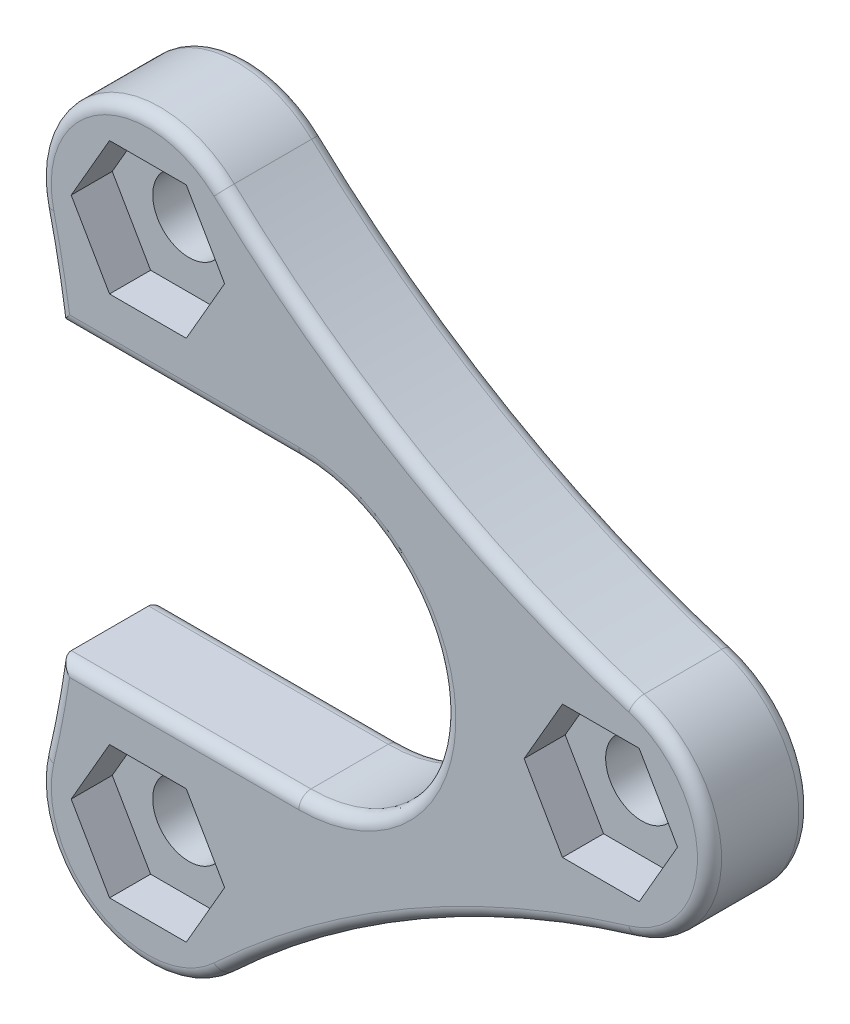
SolidWorks part; units mm, degrees
ref_plane "Front Plane" through (0, 0, 0) normal (0, 0, 1) x (1, 0, 0)
ref_plane "Top Plane" through (0, 0, 0) normal (0, 1, 0) x (1, 0, 0)
ref_plane "Right Plane" through (0, 0, 0) normal (1, 0, 0) x (0, 0, -1)
sketch "Sketch-Reference-Single" plane through (0, 0, 0) normal (0, 0, 1) x (1, 0, 0)
  circle A0 centre (-12.5, 0) radius 1.5
  circle A1 centre (-6.25, 10.8253) radius 1.5
  circle A2 centre (6.25, 10.8253) radius 1.5
  circle A3 centre (12.5, 0) radius 1.5
  circle A4 centre (6.25, -10.8253) radius 1.5
  circle A5 centre (-6.25, -10.8253) radius 1.5
  point P14 (0, 0)
sketch "Sketch-Reference-Dual" plane through (0, 0, 0) normal (0, 0, 1) x (1, 0, 0)
  line L0 (0, 0) -> (-12, 0) construction
  line L1 (0, 0) -> (0, -8.1544) construction
  circle A0 centre (-18, 10.3923) radius 1.5
  circle A1 centre (0, 0) radius 1.5
  circle A2 centre (-18, -10.3923) radius 1.5
  circle A3 centre (18, -10.3923) radius 1.5
  circle A4 centre (18, 10.3923) radius 1.5
  point P11 (-12, 0)
sketch "Sketch1" plane through (0, 0, 0) normal (0, 0, 1) x (1, 0, 0)
  line L0 (0, -8.1544) -> (0, 0) construction
  line L1 (-12, 0) -> (0, 0) construction
  line L2 (-12, 6) -> (-18.9786, 6)
  line L3 (-12, -6) -> (-18.9786, -6)
  line L4 (12, -6) -> (18.9786, -6)
  line L5 (12, 6) -> (18.9786, 6)
  line L6 (0, 0) -> (0, 10.3923) construction
  arc A0 (-12, -6) -> (-12, 6) centre (-12, 0) ccw
  arc A1 (-15.8824, -14.3629) -> (-18.9786, -6) centre (-18, -10.3923) cw
  arc A2 (15.8824, -14.3629) -> (18.9786, -6) centre (18, -10.3923) ccw
  circle A3 centre (-18, 10.3923) radius 4.5
  arc A4 (-15.8824, 14.3629) -> (-18.9786, 6) centre (-18, 10.3923) ccw
  arc A5 (12, -6) -> (12, 6) centre (12, 0) cw
  arc A6 (15.8824, 14.3629) -> (18.9786, 6) centre (18, 10.3923) cw
  arc A7 (-15.8824, 14.3629) -> (15.8824, 14.3629) centre (0, 44.1423) ccw
  arc A8 (-15.8824, -14.3629) -> (15.8824, -14.3629) centre (0, -44.1423) cw
  circle A9 centre (0, 0) radius 1.5 construction
  circle A10 centre (18, -10.3923) radius 1.5 construction
  circle A11 centre (18, 10.3923) radius 1.5 construction
  circle A12 centre (-18, 10.3923) radius 1.5 construction
  circle A13 centre (-18, -10.3923) radius 1.5 construction
  circle A14 centre (0, 0) radius 1.5
  circle A15 centre (18, -10.3923) radius 1.5
  circle A16 centre (18, 10.3923) radius 1.5
  circle A17 centre (-18, 10.3923) radius 1.5
  circle A18 centre (-18, -10.3923) radius 1.5
extrude "Boss-DualMainBody" [suppressed] add sketch "Sketch1" along normal blind 2.5
sketch "Sketch2" [suppressed] plane through (0, 0, 2.5) normal (0, 0, 1) x (1, 0, 0)
  line L0 (0, 0) -> (0, 8.3923) construction
  line L1 (-14.8246, 10.3923) -> (-16.4123, 13.1423)
  line L2 (-16.4123, 13.1423) -> (-19.5877, 13.1423)
  line L3 (-19.5877, 13.1423) -> (-21.1754, 10.3923)
  line L4 (-21.1754, 10.3923) -> (-19.5877, 7.6423)
  line L5 (-19.5877, 7.6423) -> (-16.4123, 7.6423)
  line L6 (-16.4123, 7.6423) -> (-14.8246, 10.3923)
  line L7 (14.8246, 10.3923) -> (16.4123, 7.6423)
  line L8 (16.4123, 7.6423) -> (19.5877, 7.6423)
  line L9 (19.5877, 7.6423) -> (21.1754, 10.3923)
  line L10 (21.1754, 10.3923) -> (19.5877, 13.1423)
  line L11 (19.5877, 13.1423) -> (16.4123, 13.1423)
  line L12 (16.4123, 13.1423) -> (14.8246, 10.3923)
  line L13 (14.8246, -10.3923) -> (16.4123, -13.1423)
  line L14 (16.4123, -13.1423) -> (19.5877, -13.1423)
  line L15 (19.5877, -13.1423) -> (21.1754, -10.3923)
  line L16 (21.1754, -10.3923) -> (19.5877, -7.6423)
  line L17 (19.5877, -7.6423) -> (16.4123, -7.6423)
  line L18 (16.4123, -7.6423) -> (14.8246, -10.3923)
  line L19 (-14.8246, -10.3923) -> (-16.4123, -7.6423)
  line L20 (-16.4123, -7.6423) -> (-19.5877, -7.6423)
  line L21 (-19.5877, -7.6423) -> (-21.1754, -10.3923)
  line L22 (-21.1754, -10.3923) -> (-19.5877, -13.1423)
  line L23 (-19.5877, -13.1423) -> (-16.4123, -13.1423)
  line L24 (-16.4123, -13.1423) -> (-14.8246, -10.3923)
  line L25 (0, 0) -> (-12, 0) construction
  line L27 (0, 3.1754) -> (-2.75, 1.5877)
  line L28 (-12, -6) -> (-18.9786, -6)
  line L29 (18.9786, -6) -> (12, -6)
  line L30 (12, 6) -> (18.9786, 6)
  line L31 (-18.9786, 6) -> (-12, 6)
  line L32 (-12, -6) -> (-18.9786, -6)
  line L33 (18.9786, -6) -> (12, -6)
  line L34 (12, 6) -> (18.9786, 6)
  line L35 (-18.9786, 6) -> (-12, 6)
  line L36 (-2.75, 1.5877) -> (-2.75, -1.5877)
  line L37 (-2.75, -1.5877) -> (0, -3.1754)
  line L38 (0, -3.1754) -> (2.75, -1.5877)
  line L39 (2.75, -1.5877) -> (2.75, 1.5877)
  line L40 (2.75, 1.5877) -> (0, 3.1754)
  circle A0 centre (-18, 10.3923) radius 2.75 construction
  circle A1 centre (18, 10.3923) radius 2.75 construction
  circle A2 centre (18, -10.3923) radius 2.75 construction
  circle A3 centre (-18, -10.3923) radius 2.75 construction
  arc A4 (-15.1249, 13.8541) -> (15.1249, 13.8541) centre (0, 32.0654) ccw
  arc A5 (-15.1249, -13.8541) -> (15.1249, -13.8541) centre (0, -32.0654) cw
  arc A6 (-15.8824, 14.3629) -> (15.8824, 14.3629) centre (0, 44.1423) ccw construction
  circle A7 centre (0, 0) radius 2.75 construction
  arc A12 (-12, -6) -> (-12, 6) centre (-12, 0) ccw
  arc A13 (-18.9786, -6) -> (-15.8824, -14.3629) centre (-18, -10.3923) ccw
  arc A14 (15.8824, -14.3629) -> (-15.8824, -14.3629) centre (0, -44.1423) ccw
  arc A15 (15.8824, -14.3629) -> (18.9786, -6) centre (18, -10.3923) ccw
  arc A16 (12, 6) -> (12, -6) centre (12, 0) ccw
  arc A17 (18.9786, 6) -> (15.8824, 14.3629) centre (18, 10.3923) ccw
  arc A18 (-15.8824, 14.3629) -> (15.8824, 14.3629) centre (0, 44.1423) ccw
  arc A19 (-15.8824, 14.3629) -> (-18.9786, 6) centre (-18, 10.3923) ccw
  arc A20 (-12, -6) -> (-12, 6) centre (-12, 0) ccw
  arc A21 (-18.9786, -6) -> (-15.1249, -13.8541) centre (-18, -10.3923) ccw
  arc A23 (15.1249, -13.8541) -> (18.9786, -6) centre (18, -10.3923) ccw
  arc A24 (12, 6) -> (12, -6) centre (12, 0) ccw
  arc A25 (18.9786, 6) -> (15.1249, 13.8541) centre (18, 10.3923) ccw
  arc A27 (-15.1249, 13.8541) -> (-18.9786, 6) centre (-18, 10.3923) ccw
  point P1 (0, 10.3923)
extrude "Boss-DualExtraBody" [suppressed] add sketch "Sketch2" along normal blind 1.7
fillet "Fillet-Dual" [suppressed] radius 0.5
sketch "Sketch3" plane through (0, 0, 0) normal (0, 0, 1) x (1, 0, 0)
  line L0 (0, 0) -> (4.75, 8.2272) construction
  line L1 (0, 6) -> (-9.9207, 6)
  line L2 (0, -6) -> (-9.9207, -6)
  circle A0 centre (-6.25, 10.8253) radius 1.5 construction
  circle A1 centre (12.5, 0) radius 1.5 construction
  circle A2 centre (-6.25, -10.8253) radius 1.5 construction
  circle A3 centre (-6.25, 10.8253) radius 1.5
  circle A4 centre (12.5, 0) radius 1.5
  arc A5 (13.8026, -4.3073) -> (13.8026, 4.3073) centre (12.5, 0) ccw
  circle A6 centre (-6.25, 10.8253) radius 4.5
  arc A7 (-3.1711, 14.1071) -> (-10.6316, 9.7998) centre (-6.25, 10.8253) ccw
  arc A8 (-10.6316, -9.7998) -> (-3.1711, -14.1071) centre (-6.25, -10.8253) ccw
  arc A9 (0, -6) -> (0, 6) centre (0, 0) ccw
  circle A10 centre (-6.25, -10.8253) radius 1.5
  arc A11 (-3.1711, 14.1071) -> (13.8026, 4.3073) centre (26.25, 45.4663) ccw
  arc A12 (13.8026, -4.3073) -> (-3.1711, -14.1071) centre (26.25, -45.4663) ccw
  arc A13 (-10.6316, -9.7998) -> (-9.9207, -6) centre (-52.5, 0) ccw
  arc A14 (-9.9207, 6) -> (-10.6316, 9.7998) centre (-52.5, 0) ccw
  point P30 (0, 0)
extrude "Boss-Body" add sketch "Sketch3" along normal blind 2.5
sketch "Sketch4" plane through (0, 0, 2.5) normal (0, 0, 1) x (1, 0, 0)
  line L1 (-4.6623, 13.5753) -> (-7.8377, 13.5753)
  line L2 (0, -6) -> (-9.9207, -6)
  line L3 (-9.9207, 6) -> (0, 6)
  line L4 (0, -6) -> (-9.9207, -6)
  line L5 (-9.9207, 6) -> (0, 6)
  line L6 (-7.8377, 13.5753) -> (-9.4254, 10.8253)
  line L7 (-9.4254, 10.8253) -> (-7.8377, 8.0753)
  line L8 (-7.8377, 8.0753) -> (-4.6623, 8.0753)
  line L9 (-4.6623, 8.0753) -> (-3.0746, 10.8253)
  line L10 (-3.0746, 10.8253) -> (-4.6623, 13.5753)
  line L11 (10.9123, -2.75) -> (14.0877, -2.75)
  line L12 (14.0877, -2.75) -> (15.6754, 0)
  line L13 (15.6754, 0) -> (14.0877, 2.75)
  line L14 (14.0877, 2.75) -> (10.9123, 2.75)
  line L15 (10.9123, 2.75) -> (9.3246, 0)
  line L16 (9.3246, 0) -> (10.9123, -2.75)
  line L17 (-7.8377, -13.5753) -> (-4.6623, -13.5753)
  line L18 (-4.6623, -13.5753) -> (-3.0746, -10.8253)
  line L19 (-3.0746, -10.8253) -> (-4.6623, -8.0753)
  line L20 (-4.6623, -8.0753) -> (-7.8377, -8.0753)
  line L21 (-7.8377, -8.0753) -> (-9.4254, -10.8253)
  line L22 (-9.4254, -10.8253) -> (-7.8377, -13.5753)
  circle A0 centre (-6.25, 10.8253) radius 2.75 construction
  circle A1 centre (12.5, 0) radius 2.75 construction
  circle A2 centre (-6.25, -10.8253) radius 2.75 construction
  arc A8 (0, -6) -> (0, 6) centre (0, 0) ccw
  arc A9 (-10.6316, -9.7998) -> (-9.9207, -6) centre (-52.5, 0) ccw
  arc A10 (-10.6316, -9.7998) -> (-3.1711, -14.1071) centre (-6.25, -10.8253) ccw
  arc A11 (13.8026, -4.3073) -> (-3.1711, -14.1071) centre (26.25, -45.4663) ccw
  arc A12 (13.8026, -4.3073) -> (13.8026, 4.3073) centre (12.5, 0) ccw
  arc A13 (-3.1711, 14.1071) -> (13.8026, 4.3073) centre (26.25, 45.4663) ccw
  arc A14 (-3.1711, 14.1071) -> (-10.6316, 9.7998) centre (-6.25, 10.8253) ccw
  arc A15 (-9.9207, 6) -> (-10.6316, 9.7998) centre (-52.5, 0) ccw
  arc A16 (0, -6) -> (0, 6) centre (0, 0) ccw
  arc A17 (-10.6316, -9.7998) -> (-9.9207, -6) centre (-52.5, 0) ccw
  arc A18 (-10.6316, -9.7998) -> (-3.1711, -14.1071) centre (-6.25, -10.8253) ccw
  arc A19 (13.8026, -4.3073) -> (-3.1711, -14.1071) centre (26.25, -45.4663) ccw
  arc A20 (13.8026, -4.3073) -> (13.8026, 4.3073) centre (12.5, 0) ccw
  arc A21 (-3.1711, 14.1071) -> (13.8026, 4.3073) centre (26.25, 45.4663) ccw
  arc A22 (-3.1711, 14.1071) -> (-10.6316, 9.7998) centre (-6.25, 10.8253) ccw
  arc A23 (-9.9207, 6) -> (-10.6316, 9.7998) centre (-52.5, 0) ccw
extrude "Boss-ExtraBody" add sketch "Sketch4" along normal blind 1.7
fillet "Fillet-Single" radius 0.5 20 edges at (-4.9603, 6, 0) (-4.9603, -6, 0) (-4.9603, 6, 4.2) (-4.9603, -6, 4.2) (-10.2334, -7.9079, 0) (-8.5, -14.7224, 0) (-10.2334, 7.9079, 0) (-8.5, 14.7224, 0) (4.75, 8.2272, 0) (17, 0, 0) (-10.2334, -7.9079, 4.2) (-8.5, -14.7224, 4.2) (-10.2334, 7.9079, 4.2) (-8.5, 14.7224, 4.2) (4.75, 8.2272, 4.2) (17, 0, 4.2) (6, 0, 0) (6, 0, 4.2) (4.75, -8.2272, 0) (4.75, -8.2272, 4.2)
equation "\"ScrewSize\"=3"
equation "\"D3@Sketch-Reference-Dual\" = \"ScrewSize\""
equation "\"D1@Sketch-Reference-Single\" = \"ScrewSize\""
equation "\"HotendGrooveDiameter\"=12"
equation "\"D1@Sketch1\"=\"HotendGrooveDiameter\""
equation "\"M3NutSize\"=5.5"
equation "\"D1@Sketch2\"=\"M3NutSize\""
equation "\"HotendGrooveThickness\"= \"HotendGrooveThicknessJHead\" - \"HotendGrooveWiggle\""
equation "\"D1@Boss-DualExtraBody\" = \"HotendGrooveThickness\" - 2.5"
equation "\"HotendGrooveThicknessE3d\"= 6"
equation "\"HotendGrooveThicknessJHead\"= 4.6"
equation "\"HotendGrooveWiggle\"= 0.4"
equation "\"D2@Sketch3\"=\"HotendGrooveDiameter\""
equation "\"D2@Sketch4\"=\"M3NutSize\""
equation "\"D1@Boss-ExtraBody\"=\"HotendGrooveThickness\"-2.5"
